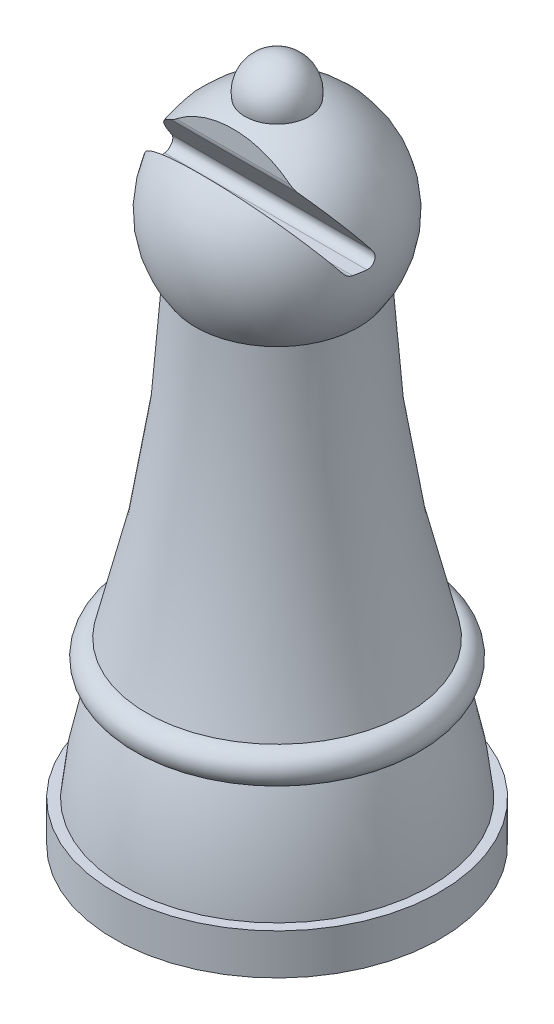
SolidWorks part; units mm, degrees
ref_plane "Front Plane" through (0, 0, 0) normal (0, 0, 1) x (1, 0, 0)
ref_plane "Top Plane" through (0, 0, 0) normal (0, 1, 0) x (1, 0, 0)
ref_plane "Right Plane" through (0, 0, 0) normal (1, 0, 0) x (0, 0, -1)
sketch "Sketch1" plane through (0, 0, 0) normal (0, 0, 1) x (1, 0, 0)
  line L0 (0, 0) -> (12.7, 0)
  line L1 (12.7, 0) -> (12.7, 3.175)
  line L2 (12.7, 3.175) -> (11.938, 3.175)
  line L3 (0, 0) -> (0, 50.8)
  line L5 (0, 50.8) -> (0, 53.34) construction
  line L6 (0, 50.8) -> (0, 53.34)
  arc A2 (10.16, 13.97) -> (10.16, 11.43) centre (10.16, 12.7) cw
  arc A4 (10.16, 11.43) -> (11.938, 3.175) centre (-19.7136, 0.6767) cw
  arc A5 (2.5073, 50.3936) -> (6.35, 38.1) centre (0, 42.8625) cw
  arc A6 (6.35, 38.1) -> (10.16, 13.97) centre (105.3561, 41.3668) ccw
  arc A7 (0, 53.34) -> (2.5073, 50.3936) centre (0, 50.8) cw
  dimension "D4" = 1.27
  dimension "D6" = 6.35
  dimension "D12" = 31.75
  dimension "D7" = 7.9375
  dimension "D13" = 99.06
  dimension "D14" = 50.8
  dimension "D1" = 12.7
  dimension "D2" = 3.175
  dimension "D3" = 0.762
  dimension "D5" = 12.7
  dimension "D8" = 38.1
  dimension "D9" = 10.16
  dimension "D10" = 10.16
  dimension "D11" = 2.54
  dimension "D15" = 2.54
revolve "Revolve1" add sketch "Sketch1" angle 360 about L3
ref_plane "Plane1" through (0, 48.26, 0) normal (0, 1, 0) x (1, 0, 0)
sketch "Sketch4" plane through (0, 48.26, 0) normal (0, 1, 0) x (1, 0, 0)
  line L1 (-8.89, -3.429) -> (8.89, -3.429)
  line L2 (-8.89, -3.429) -> (-8.89, -5.969)
  line L3 (-8.89, -5.969) -> (8.89, -5.969)
  line L4 (8.89, -3.429) -> (8.89, -5.969)
  circle A0 centre (0, 0) radius 7.9375 construction
  point P4 (8.89, -4.699)
  dimension "D1" = 2.54
  dimension "D2" = 17.78
  dimension "D3" = 8.89
  dimension "D4" = 3.429
sketch "Sketch5" plane through (0, 0, 0) normal (1, 0, 0) x (0, 0, -1)
  line L0 (-1.3945, 41.3515) -> (-7.6195, 54.1127) construction
  line L1 (6.35, 38.1) -> (-6.35, 38.1) construction
  dimension "D1" = 3.2515
  dimension "D2" = 12.7613
  dimension "D3" = 6.225
  dimension "D4" = 1.3945
ref_plane "Plane2" through (0, 0, 0) normal (-1, 0, 0) x (0, 0.8988, 0.4384)
ref_plane "Plane3" through (0, 7.3989, -15.1677) normal (0, -0.4384, 0.8988) x (0, 0.8988, 0.4384)
ref_plane "Plane4" through (0, 43.18, 0) normal (0, 1, 0) x (1, 0, 0)
sketch "Sketch6" plane through (0, 43.18, 0) normal (0, 1, 0) x (1, 0, 0)
  line L0 (-8.89, -3.429) -> (-8.89, -5.969) construction
  line L1 (-8.89, -2.159) -> (8.89, -2.159)
  line L2 (-8.89, -2.159) -> (-8.89, 0.381)
  line L3 (-8.89, 0.381) -> (8.89, 0.381)
  line L4 (8.89, -2.159) -> (8.89, 0.381)
  line L5 (-8.89, -3.429) -> (8.89, -3.429) construction
  point P4 (-8.89, -0.889)
  dimension "D1" = 2.54
  dimension "D2" = 17.78
  dimension "D3" = 0
  dimension "D4" = 1.27
loft "Cut-Loft1" cut profiles "Sketch4", "Sketch6"
extrude "Cut-Extrude4" cut sketch "Sketch4<2>" along normal blind 10.795
sketch "Sketch4<2>" plane through (0, 48.26, 0) normal (0, 1, 0) x (1, 0, 0) same geometry as "Sketch4"
fillet "Fillet1" radius 0.635 3 edges
